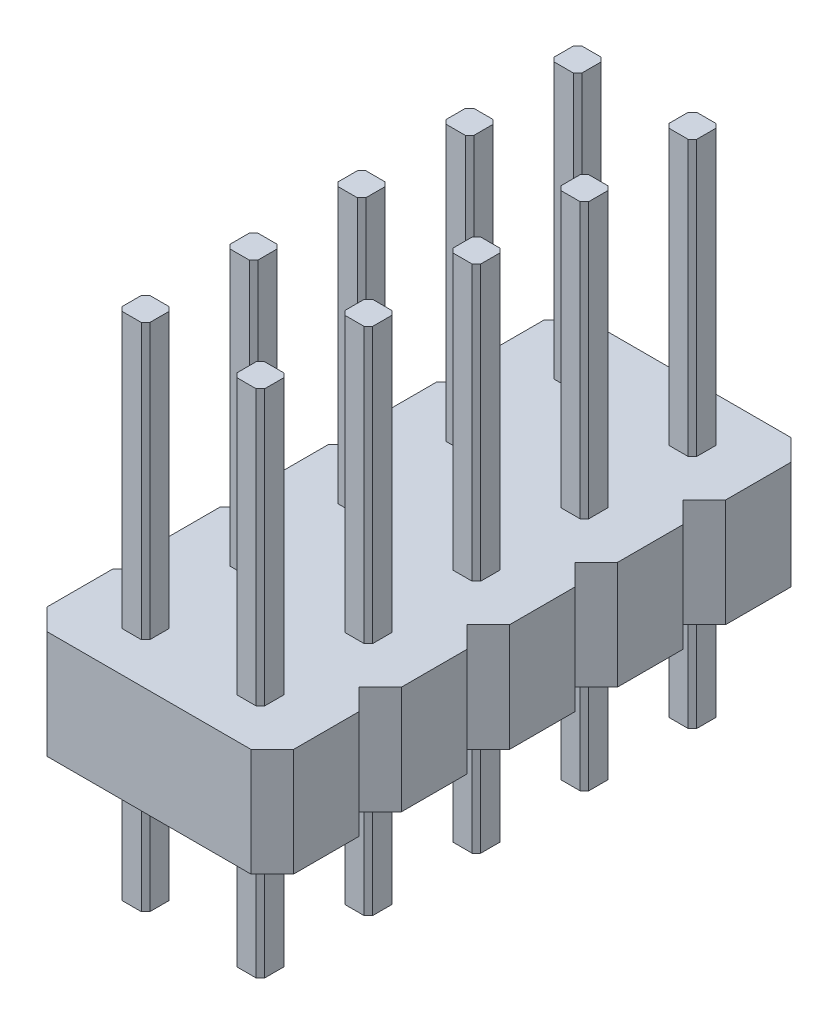
SolidWorks part; units mm, degrees
ref_plane "Front Plane" through (0, 0, 0) normal (0, 0, 1) x (1, 0, 0)
ref_plane "Top Plane" through (0, 0, 0) normal (0, 1, 0) x (1, 0, 0)
ref_plane "Right Plane" through (0, 0, 0) normal (1, 0, 0) x (0, 0, -1)
sketch "Sketch1" plane through (0, 0, 0) normal (0, 1, 0) x (1, 0, 0)
  line L0 (-0.325, 0.225) -> (-0.225, 0.325)
  line L1 (-0.225, -0.325) -> (0.225, -0.325)
  line L2 (-0.325, -0.225) -> (-0.325, 0.225)
  line L3 (-0.225, 0.325) -> (0.225, 0.325)
  line L4 (0.325, -0.225) -> (0.325, 0.225)
  line L5 (-0.325, -0.325) -> (0.325, 0.325) construction
  line L6 (-0.325, 0.325) -> (0.325, -0.325) construction
  line L7 (0.225, 0.325) -> (0.325, 0.225)
  line L8 (0.225, -0.325) -> (0.325, -0.225)
  line L9 (-0.325, -0.225) -> (-0.225, -0.325)
  line L10 (2.375, -0.225) -> (2.375, 0.225)
  line L11 (2.375, -0.225) -> (2.475, -0.325)
  line L12 (2.375, 0.225) -> (2.475, 0.325)
  line L13 (2.475, -0.325) -> (2.925, -0.325)
  line L14 (2.925, -0.325) -> (3.025, -0.225)
  line L15 (3.025, -0.225) -> (3.025, 0.225)
  line L16 (2.925, 0.325) -> (3.025, 0.225)
  line L17 (2.475, 0.325) -> (2.925, 0.325)
  point P0 (0, 0)
  dimension "D1" = 0.65
  dimension "D2" = 0.65
  dimension "D4" = 2.7
  dimension "D3" = 2
extrude "Boss-Extrude2" add sketch "Sketch1" along normal blind 12
ref_plane "Plane1" through (0, 3, 0) normal (0, -1, 0) x (-1, 0, 0)
sketch "Sketch2" plane through (0, 3, 0) normal (0, -1, 0) x (-1, 0, 0)
  line L0 (0.325, 0) -> (-3.025, 0) construction
  line L1 (0.325, 0.225) -> (0.325, -0.225) construction
  line L2 (-3.025, -0.225) -> (-3.025, 0.225) construction
  line L3 (-4.25, 0.77) -> (-3.75, 1.27)
  line L4 (-3.75, -1.27) -> (1.05, -1.27)
  line L5 (-4.25, -0.77) -> (-4.25, 0.77)
  line L6 (-3.75, 1.27) -> (1.05, 1.27)
  line L7 (1.55, -0.77) -> (1.55, 0.77)
  line L8 (-4.25, -1.27) -> (1.55, 1.27) construction
  line L9 (-4.25, 1.27) -> (1.55, -1.27) construction
  line L10 (-4.25, -0.77) -> (-3.75, -1.27)
  line L11 (1.05, -1.27) -> (1.55, -0.77)
  line L12 (1.05, 1.27) -> (1.55, 0.77)
  point P6 (-1.35, 0)
  dimension "D1" = 5.8
  dimension "D2" = 2.54
extrude "Boss-Extrude3" add sketch "Sketch2" against normal blind 2.54
pattern_linear "LPattern1" count 5 spacing 2.54 along (0, 0, -1) of "Boss-Extrude3"
pattern_linear "LPattern2" count 5 spacing 2.54 along (0, 0, -1) of "Boss-Extrude2"
